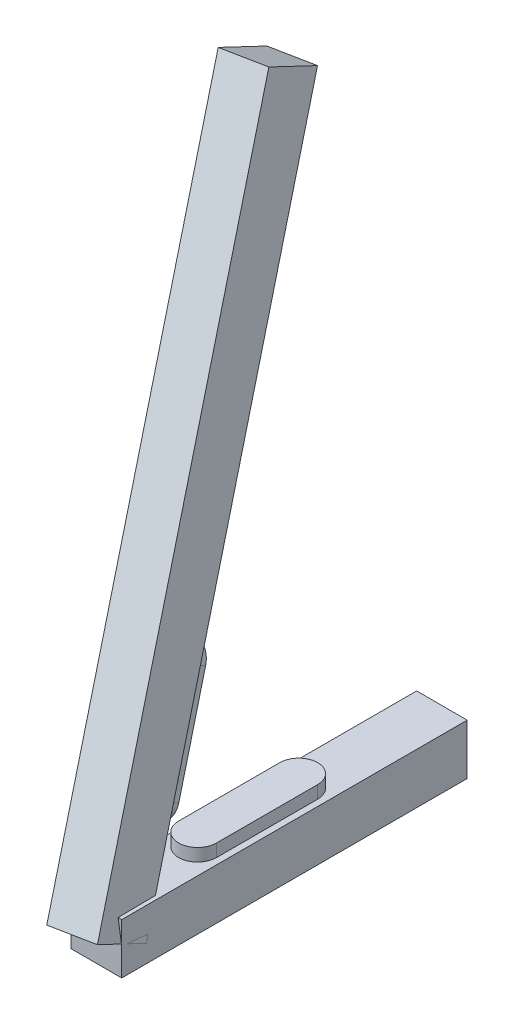
SolidWorks part; units mm, degrees
material "6061-T6 (SS)"
ref_plane "Front Plane" through (0, 0, 0) normal (0, 0, 1) x (1, 0, 0)
ref_plane "Top Plane" through (0, 0, 0) normal (0, 1, 0) x (1, 0, 0)
ref_plane "Right Plane" through (0, 0, 0) normal (1, 0, 0) x (0, 0, -1)
sketch3d "3DSketch1"
  line L0 (0, 0, 53.4911) -> (0, 0, -53.4911) construction
  line L1 (0, 41.3657, 0) -> (0, -41.3657, 0) construction
  line L2 (0, 0, 0) -> (0, 0, -173.5135)
  line L3 (0, 0, 0) -> (0, 193.5554, -88.0535) construction
  line L4 (0, 0, 0) -> (-46.7361, 291.9678, -132.824)
  line L5 (-12.7, -12.7, 0) -> (12.7, -12.7, 0)
  line L6 (-12.7, -12.7, 0) -> (-12.7, 12.7, 0)
  line L7 (-12.7, 12.7, 0) -> (12.7, 12.7, 0)
  line L8 (12.7, -12.7, 0) -> (12.7, 12.7, 0)
  line L9 (-12.7, -12.7, 0) -> (12.7, 12.7, 0) construction
  line L10 (-12.7, 12.7, 0) -> (12.7, -12.7, 0) construction
  line L17 (36.9794, 4.9044, -2.2311) -> (-38.1106, -5.0544, 2.2994) construction
  line L18 (-13.1889, 3.2361, 11.7541) -> (-11.9133, -7.0991, -11.413)
  line L19 (-13.1889, 3.2361, 11.7541) -> (11.9133, 7.0991, 11.413)
  line L20 (11.9133, 7.0991, 11.413) -> (13.1889, -3.2361, -11.7541)
  line L21 (-11.9133, -7.0991, -11.413) -> (13.1889, -3.2361, -11.7541)
  line L22 (-13.1889, 3.2361, 11.7541) -> (13.1889, -3.2361, -11.7541) construction
  line L23 (11.9133, 7.0991, 11.413) -> (-11.9133, -7.0991, -11.413) construction
  line L24 (0, 0, 0) -> (-12.5511, -1.9315, 0.1706) construction
  point P4 (0, 0, 0)
  point P20 (-275.5937, 328.5019, -192.6183)
  point P21 (-275.5937, 328.5019, -192.6183)
  point P22 (-289.3483, 256.3983, -173.6656)
  point P24 (-46.7361, 291.9678, -132.824)
  dimension "D1" = 173.17
  dimension "D2" = 25.4
  dimension "D4" = 114.19
  dimension "D3" = 65.99
sketch3d "bracket"
  line L0 (-11.9133, -7.0991, -11.413) -> (13.1889, -3.2361, -11.7541) construction
  line L1 (0, 0, 0) -> (-46.7361, 291.9678, -132.824) construction
  line L2 (-12.7, 12.7, 0) -> (12.7, 12.7, 0) construction
  line L3 (0, 0, 0) -> (0, 0, -173.5135) construction
  line L4 (-11.9133, -7.0991, -11.413) -> (13.1889, -3.2361, -11.7541)
  line L9 (-11.9133, -7.0991, -11.413) -> (-58.6494, 284.8687, -144.237)
  line L10 (13.1889, -3.2361, -11.7541) -> (-33.5471, 288.7317, -144.5781)
  line L11 (-58.6494, 284.8687, -144.237) -> (-33.5471, 288.7317, -144.5781)
  line L12 (12.7, 12.7, 0) -> (-12.7, 12.7, 0)
  line L13 (12.7, 12.7, 0) -> (12.7, 12.7, -173.5135)
  line L14 (-12.7, 12.7, 0) -> (-12.7, 12.7, -173.5135)
  line L15 (12.7, 12.7, -173.5135) -> (-12.7, 12.7, -173.5135)
  line L16 (0, 12.7, -173.5135) -> (0, 12.7, 0) construction
  line L17 (0.6378, -5.1676, -11.5836) -> (-46.0982, 286.8002, -144.4075) construction
  line L18 (0, 12.7, -101.6) -> (0, 12.7, -50.8)
  line L19 (-6.6866, 40.5892, -32.3996) -> (-14.011, 86.3461, -53.2156)
  line L20 (9.525, 12.7, -101.6) -> (9.525, 12.7, -50.8)
  line L21 (-9.525, 12.7, -101.6) -> (-9.525, 12.7, -50.8)
  line L22 (-23.4243, 84.8974, -53.0877) -> (-16.0999, 39.1406, -32.2717)
  line L23 (-4.5977, 87.7947, -53.3435) -> (2.7267, 42.0379, -32.5275)
  line L24 (-14.011, 86.3461, -53.2156) -> (-23.4243, 84.8974, -53.0877) construction
  line L25 (-14.011, 86.3461, -53.2156) -> (-13.6921, 83.7623, -59.0074) construction
  line L26 (-9.525, 12.7, -101.6) -> (0, 12.7, -101.6) construction
  line L27 (0, 12.7, -101.6) -> (0, 19.05, -101.6) construction
  circle A1 centre (0, 12.7, -50.8) radius 3.175
  circle A2 centre (0, 12.7, -101.6) radius 3.175
  circle A3 centre (-14.011, 86.3461, -53.2156) radius 3.175
  circle A4 centre (-6.6866, 40.5892, -32.3996) radius 3.175
  circle A5 centre (0, 12.7, -50.8) radius 9.525
  circle A6 centre (0, 12.7, -101.6) radius 9.525
  circle A7 centre (-14.011, 86.3461, -53.2156) radius 9.525
  circle A8 centre (-6.6866, 40.5892, -32.3996) radius 9.525
  point P12 (12.7, 12.7, 0)
  point P13 (-12.7, 12.7, 0)
  point P22 (0, 9.525, -50.8)
  point P31 (0, 9.525, -101.6)
  point P35 (-14.1705, 87.638, -50.3197)
  point P37 (-6.846, 41.8811, -29.5037)
  point P39 (0, 3.175, -50.8)
  point P41 (0, 3.175, -101.6)
  point P43 (-14.4894, 90.2218, -44.5279)
  point P45 (-7.165, 44.4649, -23.7119)
  point P46 (0, 12.7, -47.625)
  point P47 (0, 12.7, -41.275)
  point P58 (0, 12.7, -76.2)
  point P59 (-10.3488, 63.4677, -42.8076)
  dimension "D1" = 50.8
  dimension "D3" = 6.35
  dimension "D2" = 50.8
  dimension "D4" = 50.8
  dimension "D5" = 50.8
  dimension "D6" = 6.35
  dimension "D7" = 6.35
  dimension "D8" = 6.35
sketch3d "3DSketch3"
  line L0 (-10.3488, 63.4677, -42.8076) -> (0, 12.7, -76.2)
  line L1 (3.9199, 15.9784, -79.9695) -> (0, 12.7, -76.2)
  line L2 (4.8806, 11.2093, -72.4211) -> (0, 12.7, -76.2)
  circle A0 centre (0, 12.7, -76.2) radius 6.35
  point P5 (-1.0661, 17.9299, -72.76)
  dimension "D1" = 12.7
sketch3d "3DSketch4"
  line L0 (-10.9454, 66.6035, -51.2014) -> (-9.1143, 55.1643, -45.9974)
  line L1 (-13.6921, 83.7623, -59.0074) -> (-6.3677, 38.0055, -38.1914) construction
  line L2 (0, 19.05, -101.6) -> (0, 19.05, -50.8) construction
  line L3 (-6.6866, 40.5892, -32.3996) -> (-14.011, 86.3461, -53.2156) construction
  line L7 (0, 12.7, -101.6) -> (0, 12.7, -50.8) construction
  line L8 (0, 19.05, -82.55) -> (0, 19.05, -69.85)
  circle A0 centre (-10.9454, 66.6035, -51.2014) radius 9.525
  circle A1 centre (-9.1143, 55.1643, -45.9974) radius 9.525
  circle A9 centre (-6.6866, 40.5892, -32.3996) radius 9.525 construction
  circle A10 centre (0, 19.05, -69.85) radius 9.525
  circle A11 centre (0, 19.05, -82.55) radius 9.525
  point P4 (-10.0299, 60.8839, -48.5994)
  point P7 (-10.0299, 60.8839, -48.5994)
  point P8 (-10.0299, 60.8839, -48.5994)
  point P10 (-11.4238, 70.4792, -42.5137)
  point P12 (-9.5927, 59.0399, -37.3097)
  point P15 (-7.165, 44.4649, -23.7119)
  point P24 (0, 19.05, -76.2)
  point P25 (0, 19.05, -76.2)
  point P27 (0, 28.575, -69.85)
  point P29 (0, 28.575, -82.55)
  dimension "D1" = 12.7
sketch "Sketch1" plane through (0, 0, 0) normal (0, 0, 1) x (1, 0, 0)
  line L0 (-12.7, -12.7) -> (12.7, -12.7) construction
  line L1 (-12.7, -12.7) -> (-12.7, 12.7) construction
  line L2 (-12.7, 12.7) -> (12.7, 12.7) construction
  line L3 (12.7, -12.7) -> (12.7, 12.7) construction
  line L4 (-12.7, -12.7) -> (12.7, -12.7)
  line L5 (-12.7, -12.7) -> (-12.7, 12.7)
  line L6 (-12.7, 12.7) -> (12.7, 12.7)
  line L7 (12.7, -12.7) -> (12.7, 12.7)
extrude "Boss-Extrude1" add sketch "Sketch1" against normal up to vertex (173.5135 mm away) up to point (0, 0, -173.5135)
sketch "Sketch2" plane through (0, 0, 0) normal (-0.1442, 0.9007, -0.4098) x (0.9834, 0.0843, -0.1607)
  line L0 (-14.5859, -10.4801) -> (10.4801, -14.5859) construction
  line L1 (-14.5859, -10.4801) -> (-10.4801, 14.5859) construction
  line L2 (-10.4801, 14.5859) -> (14.5859, 10.4801) construction
  line L3 (10.4801, -14.5859) -> (14.5859, 10.4801) construction
  line L4 (-14.5859, -10.4801) -> (10.4801, -14.5859)
  line L5 (-14.5859, -10.4801) -> (-10.4801, 14.5859)
  line L6 (-10.4801, 14.5859) -> (14.5859, 10.4801)
  line L7 (10.4801, -14.5859) -> (14.5859, 10.4801)
extrude "Boss-Extrude2" add sketch "Sketch2" along normal up to vertex (324.1476 mm away) separate body up to point (-46.7361, 291.9678, -132.824)
sketch "Sketch3" plane through (0.6378, -5.1676, -11.5836) normal (-0.0502, 0.4069, 0.9121) x (0.9987, 0.0208, 0.0457)
  line L0 (-24.056, 99.1695) -> (-16.7408, 48.899) construction
  line L1 (-5.2045, 101.9127) -> (2.1106, 51.6421) construction
  line L2 (-24.056, 99.1695) -> (-16.7408, 48.899)
  line L3 (-5.2045, 101.9127) -> (2.1106, 51.6421)
  circle A0 centre (-7.3151, 50.2706) radius 9.525 construction
  circle A1 centre (-14.6302, 100.5411) radius 9.525 construction
  arc A2 (-16.7408, 48.899) -> (2.1106, 51.6421) centre (-7.3151, 50.2706) ccw
  arc A3 (-5.2045, 101.9127) -> (-24.056, 99.1695) centre (-14.6302, 100.5411) ccw
extrude "Boss-Extrude3" add sketch "Sketch3" against normal up to vertex (6.35 mm away) from vertex separate body up to point (-13.6921, 83.7623, -59.0074) starting at point (-14.011, 86.3461, -53.2156)
sketch "Sketch4" plane through (0, 12.7, 0) normal (0, -1, 0) x (-1, 0, 0)
  line L0 (-9.525, 101.6) -> (-9.525, 50.8) construction
  line L1 (9.525, 101.6) -> (9.525, 50.8) construction
  line L2 (-9.525, 101.6) -> (-9.525, 50.8)
  line L3 (9.525, 101.6) -> (9.525, 50.8)
  circle A0 centre (0, 50.8) radius 9.525 construction
  circle A1 centre (0, 101.6) radius 9.525 construction
  arc A2 (-9.525, 50.8) -> (9.525, 50.8) centre (0, 50.8) ccw
  arc A3 (9.525, 101.6) -> (-9.525, 101.6) centre (0, 101.6) ccw
  point P8 (0, 0)
  point P9 (0, 0)
extrude "Boss-Extrude4" add sketch "Sketch4" against normal up to vertex (6.35 mm away) from vertex separate body up to point (0, 19.05, -101.6) starting at point (0, 12.7, -101.6)
sketch "Sketch5" plane through (5.1744, -25.3838, -16.6962) normal (-0.1679, 0.8236, 0.5417) x (0.4628, -0.4194, 0.781)
  circle A0 centre (-64.8372, 28.5305) radius 6.35 construction
  circle A1 centre (-64.8372, 28.5305) radius 6.35
extrude "Boss-Extrude5" [suppressed] add sketch "Sketch5" along normal up to surface (54.5052 mm away) from surface
sketch "Sketch6" plane through (0, 19.05, 0) normal (0, 1, 0) x (1, 0, 0)
  line L2 (-9.525, 82.55) -> (-9.525, 69.85)
  line L3 (9.525, 82.55) -> (9.525, 69.85)
  circle A0 centre (0, 82.55) radius 9.525 construction
  circle A1 centre (0, 82.55) radius 9.525
  arc A2 (9.525, 82.55) -> (-9.525, 82.55) centre (0, 82.55) ccw
  circle A3 centre (0, 69.85) radius 9.525
  arc A4 (-9.525, 69.85) -> (9.525, 69.85) centre (0, 69.85) ccw
  circle A5 centre (0, 69.85) radius 9.525 construction
  arc A6 (9.525, 82.55) -> (-9.525, 82.55) centre (0, 82.55) ccw
  arc A7 (-9.525, 69.85) -> (9.525, 69.85) centre (0, 69.85) ccw
  dimension "D1" = 85.2473
  dimension "D3" = 0
  dimension "D4" = 0
sketch "Sketch7" plane through (0.9567, -7.7514, -17.3754) normal (-0.0502, 0.4069, 0.9121) x (0.9987, 0.0205, 0.0459)
  line L3 (-2.492, 83.0603) -> (-0.6586, 70.4934)
  line L4 (-21.3424, 80.3102) -> (-19.509, 67.7432)
  circle A0 centre (-11.9172, 81.6853) radius 9.525 construction
  circle A1 centre (-10.0838, 69.1183) radius 9.525
  arc A2 (-19.509, 67.7432) -> (-0.6586, 70.4934) centre (-10.0838, 69.1183) ccw
  circle A3 centre (-11.9172, 81.6853) radius 9.525
  arc A4 (-2.492, 83.0603) -> (-21.3424, 80.3102) centre (-11.9172, 81.6853) ccw
  circle A5 centre (-10.0838, 69.1183) radius 9.525 construction
  arc A6 (-2.492, 83.0603) -> (-21.3424, 80.3102) centre (-11.9172, 81.6853) ccw
  arc A7 (-19.509, 67.7432) -> (-0.6586, 70.4934) centre (-10.0838, 69.1183) ccw
  dimension "D1" = 0
  dimension "D2" = 0
equation "\"D1@bracket\"=\"D2@bracket\""
